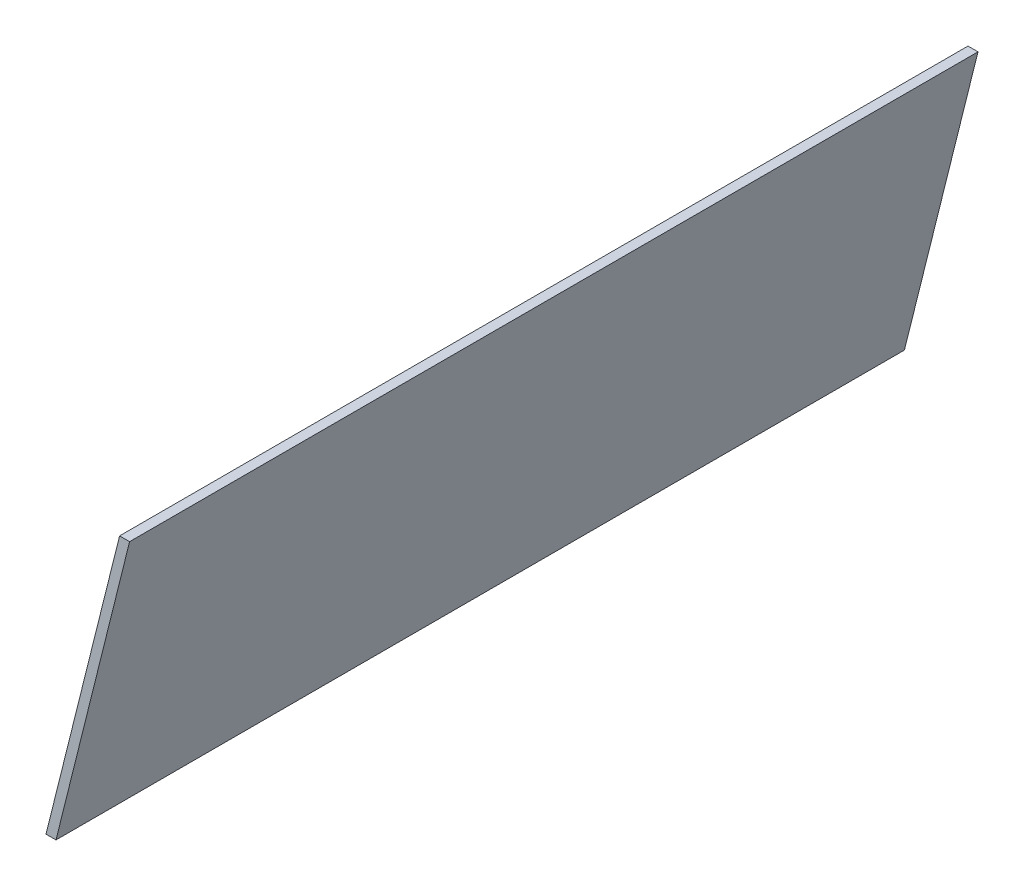
SolidWorks part; units mm, degrees
material "5052-H34"
ref_plane "Front Plane" through (0, 0, 0) normal (0, 0, 1) x (1, 0, 0)
ref_plane "Top Plane" through (0, 0, 0) normal (0, 1, 0) x (1, 0, 0)
ref_plane "Right Plane" through (0, 0, 0) normal (1, 0, 0) x (0, 0, -1)
sketch "Sketch1" plane through (0, 0, 0) normal (0, 0, 1) x (1, 0, 0)
  line L0 (-40.9017, -38.8249) -> (-37.6295, -38.8249)
  line L1 (-37.6295, -38.8249) -> (-13.5631, 57.7001)
  line L2 (-40.9017, -38.8249) -> (-16.8353, 57.7001)
  line L3 (-13.5631, 57.7001) -> (-16.8353, 57.7001)
  dimension "D1" = 104
  dimension "D2" = 96.525
  dimension "D3" = 3.175
extrude "Boss-Extrude1" add sketch "Sketch1" along normal blind 277.475 contours L1 L3 L2 L0
